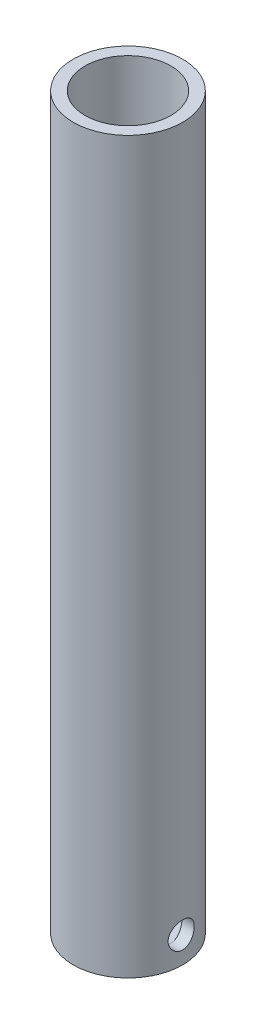
SolidWorks part; units mm, degrees
material "6063-T5"
ref_plane "Front Plane" through (0, 0, 0) normal (0, 0, 1) x (1, 0, 0)
ref_plane "Top Plane" through (0, 0, 0) normal (0, 1, 0) x (1, 0, 0)
ref_plane "Right Plane" through (0, 0, 0) normal (1, 0, 0) x (0, 0, -1)
sketch "Sketch1" plane through (0, 0, 0) normal (0, 1, 0) x (1, 0, 0)
  circle A0 centre (0, 0) radius 10.4648
  circle A1 centre (0, 0) radius 13.335
  dimension "D1" = 20.9296
  dimension "D2" = 26.67
extrude "Boss-Extrude1" add sketch "Sketch1" along normal blind 177.8
extrude "Boss-Extrude2" add sketch "Sketch1<2>" along normal blind 3.175 contours A0
sketch "Sketch1<2>" plane through (0, 0, 0) normal (0, 1, 0) x (1, 0, 0) same geometry as "Sketch1"
ref_plane "Plane1" through (13.335, 0, 0) normal (1, 0, 0) x (0, 0, -1)
sketch "Sketch3" plane through (13.335, 0, 0) normal (1, 0, 0) x (0, 0, -1)
  line L0 (0, -177.8) -> (0, 177.8) construction
  line L1 (13.335, 177.8) -> (-13.335, 177.8) construction
  line L2 (-13.335, 0) -> (13.335, 0) construction
  circle A0 centre (0, 6.35) radius 3.175
  point P0 (0, 6.35)
  point P6 (0, 0)
  dimension "D2" = 6.35
  dimension "D1" = 6.35
extrude "Cut-Extrude1" cut sketch "Sketch3" against normal blind 14.351
